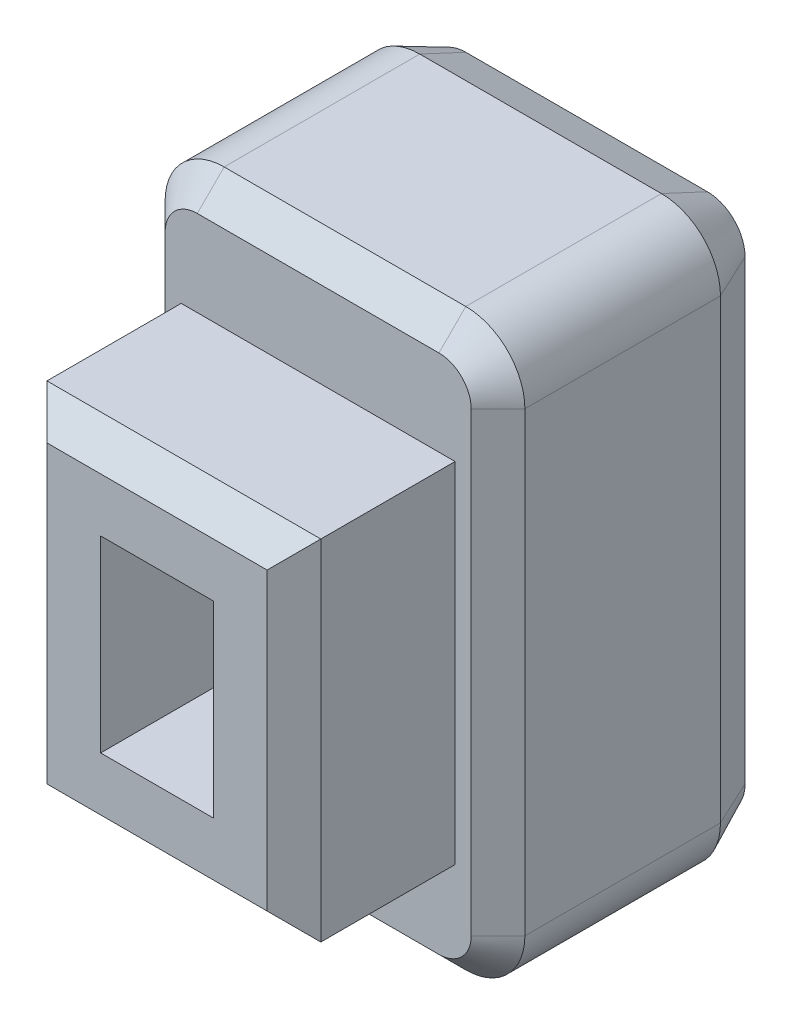
SolidWorks part; units mm, degrees
ref_plane "Plan de face" through (0, 0, 0) normal (0, 0, 1) x (1, 0, 0)
ref_plane "Plan de dessus" through (0, 0, 0) normal (0, 1, 0) x (1, 0, 0)
ref_plane "Plan de droite" through (0, 0, 0) normal (1, 0, 0) x (0, 0, -1)
sketch "Esquisse2" plane through (0, 0, 0) normal (0, 0, 1) x (1, 0, 0)
  line L1 (1.1, 0) -> (5.6, 0)
  line L2 (0, 1.1) -> (0, 9.6)
  line L3 (1.1, 10.7) -> (5.6, 10.7)
  line L4 (6.7, 1.1) -> (6.7, 9.6)
  arc A0 (5.6, 10.7) -> (6.7, 9.6) centre (5.6, 9.6) cw
  arc A1 (5.6, 0) -> (6.7, 1.1) centre (5.6, 1.1) ccw
  arc A2 (1.1, 0) -> (0, 1.1) centre (1.1, 1.1) cw
  arc A3 (0, 9.6) -> (1.1, 10.7) centre (1.1, 9.6) cw
  point P7 (6.7, 10.7)
  point P12 (0, 0)
  point P15 (0, 10.7)
  dimension "D3" = 1.1
  dimension "D1" = 6.7
  dimension "D2" = 10.7
extrude "Boss.-Extru.1" add sketch "Esquisse2" along normal blind 8
sketch "Esquisse3" plane through (0, 0, 8) normal (0, 0, 1) x (1, 0, 0)
  line L1 (2.3, 7.1) -> (4.4, 7.1)
  line L2 (2.3, 3.6) -> (2.3, 7.1)
  line L3 (4.4, 3.6) -> (4.4, 7.1)
  line L4 (6.7, 1.1) -> (6.7, 9.6) construction
  line L6 (5.6, 10.7) -> (1.1, 10.7) construction
  line L7 (0, 9.6) -> (0, 1.1) construction
  line L8 (1.1, 0) -> (5.6, 0) construction
  line L11 (2.3, 3.6) -> (4.4, 3.6)
  line L13 (-7.1761, 5.2) -> (15.2275, 5.2) construction
  dimension "D2" = 2.1
  dimension "D3" = 3.5
  dimension "D4" = 2.3
  dimension "D5" = 3.6
  dimension "D6" = 2.3
  dimension "D9" = 3.6
  dimension "D10" = 5.5
chamfer "Chanfrein1" distance 0.4 angle 65 8 edges at (3.35, 0, 0) (6.3778, 0.3222, 0) (0.3222, 0.3222, 0) (6.7, 5.35, 0) (0, 5.35, 0) (6.3778, 10.3778, 0) (0.3222, 10.3778, 0) (3.35, 10.7, 0) first distance on face at (3.35, 5.35, 0)
extrude "Enlèv. mat.-Extru.4" cut sketch "Esquisse3" against normal blind 3
sketch "Esquisse4" plane through (0, 0, 8) normal (0, 0, 1) x (1, 0, 0)
  line L0 (4.4, 3.6) -> (4.4, 7.1) construction
  line L1 (5.9, 2.1) -> (0.8, 2.1)
  line L2 (5.9, 2.1) -> (5.9, 8.6)
  line L3 (5.9, 8.6) -> (0.8, 8.6)
  line L4 (0.8, 2.1) -> (0.8, 8.6)
  line L5 (2.3, 3.6) -> (4.4, 3.6) construction
  line L6 (2.3, 7.1) -> (2.3, 3.6) construction
  line L7 (4.4, 7.1) -> (2.3, 7.1) construction
  dimension "D1" = 1.5
  dimension "D2" = 1.5
  dimension "D3" = 1.5
  dimension "D4" = 1.5
extrude "Enlèv. mat.-Extru.5" cut sketch "Esquisse4" against normal blind 3 flip side to cut
chamfer "Chanfrein2" distance 0.5 angle 45 12 edges at (6.7, 5.35, 5) (6.3778, 10.3778, 5) (6.3778, 0.3222, 5) (3.35, 10.7, 5) (3.35, 0, 5) (0.3222, 10.3778, 5) (0.3222, 0.3222, 5) (0, 5.35, 5) (5.9, 5.35, 8) (3.35, 8.6, 8) (0.8, 5.35, 8) (3.35, 2.1, 8)
sketch "Esquisse5" plane through (0, 0, 0) normal (0, 0, -1) x (-1, 0, 0)
  line L0 (-0.4, 4.5075) -> (-6.3, 4.5075) construction
  line L1 (-0.4, 1.1) -> (-0.4, 9.6) construction
  line L2 (-6.3, 9.6) -> (-6.3, 1.1) construction
  line L3 (-3.375, -0.9158) -> (-3.375, 11.6549) construction
  line L4 (-3.375, 5.1122) -> (-2.775, 6.1122)
  line L5 (-2.775, 6.1122) -> (-3.175, 6.1122)
  line L6 (-3.175, 6.1122) -> (-3.175, 8.8488)
  line L7 (-3.175, 8.8488) -> (-2.775, 8.8488)
  line L8 (-2.775, 8.8488) -> (-3.375, 9.8488)
  line L9 (-3.375, 9.8488) -> (-3.975, 8.8488)
  line L10 (-3.975, 8.8488) -> (-3.575, 8.8488)
  line L11 (-3.575, 8.8488) -> (-3.575, 6.1122)
  line L12 (-3.575, 6.1122) -> (-4.005, 6.1122)
  line L13 (-4.005, 6.1122) -> (-3.375, 5.1122)
  text T0 "<b>V</b>" font "Century Gothic" height 3.5
  dimension "D1" = 0.4
  dimension "D2" = 0.2
  dimension "D3" = 1
  dimension "D4" = 1
  dimension "D5" = 1
  dimension "D6" = 1
  dimension "D7" = 0.4
  dimension "D8" = 0.4
  dimension "D9" = 0.4
  dimension "D10" = 0.43
extrude "Boss.-Extru.2" add sketch "Esquisse5" along normal blind 0.2
extrude "Enlèv. mat.-Extru.6" cut sketch "Esquisse5<2>" against normal blind 0.2
sketch "Esquisse5<2>" plane through (0, 0, 0) normal (0, 0, -1) x (-1, 0, 0) same geometry as "Esquisse5"
